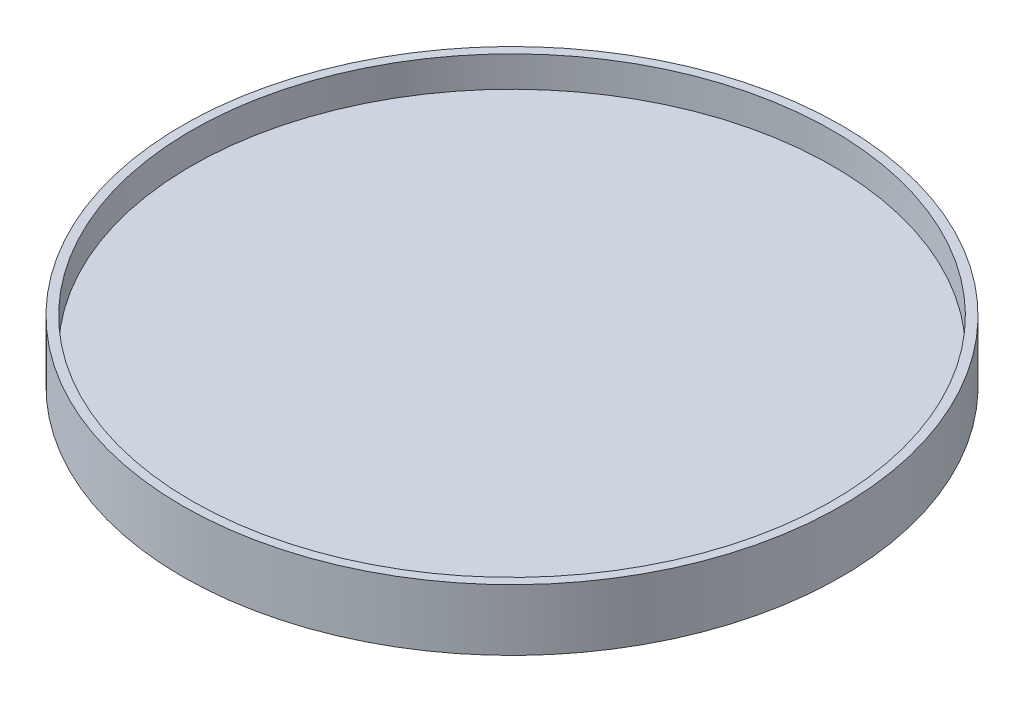
SolidWorks part; units mm, degrees
ref_plane "Front Plane" through (0, 0, 0) normal (0, 0, 1) x (1, 0, 0)
ref_plane "Top Plane" through (0, 0, 0) normal (0, 1, 0) x (1, 0, 0)
ref_plane "Right Plane" through (0, 0, 0) normal (1, 0, 0) x (0, 0, -1)
sketch "Sketch1" plane through (0, 0, 0) normal (0, 1, 0) x (1, 0, 0)
  circle A0 centre (0, 0) radius 34.1376
  dimension "D1" = 68.2752
extrude "Boss-Extrude1" add sketch "Sketch1" along normal blind 6.35
sketch "Sketch2" plane through (0, 6.35, 0) normal (0, 1, 0) x (1, 0, 0)
  circle A0 centre (0, 0) radius 33.2105
extrude "Cut-Extrude3" cut sketch "Sketch2" against normal blind 3.175
